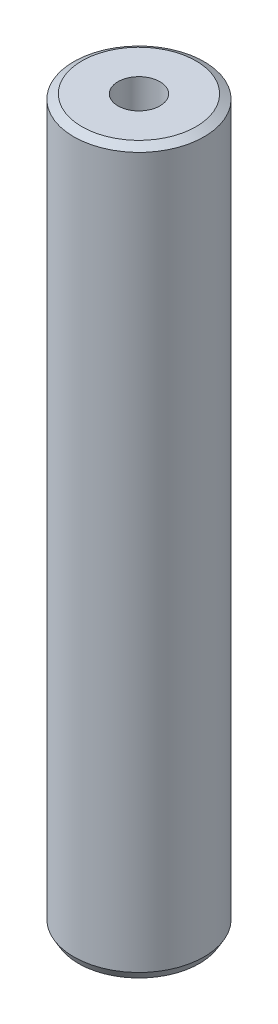
SolidWorks part; units mm, degrees
ref_plane "Front Plane" through (0, 0, 0) normal (0, 0, 1) x (1, 0, 0)
ref_plane "Top Plane" through (0, 0, 0) normal (0, 1, 0) x (1, 0, 0)
ref_plane "Right Plane" through (0, 0, 0) normal (1, 0, 0) x (0, 0, -1)
sketch "Sketch1" plane through (0, 0, 0) normal (0, 1, 0) x (1, 0, 0)
  circle A0 centre (0, 0) radius 25
  dimension "SHAFT_OD" = 50
extrude "Boss-Extrude1" add sketch "Sketch1" along normal blind 277.3595
sketch "Sketch2" plane through (0, 0, 0) normal (0, 1, 0) x (1, 0, 0)
  circle A0 centre (0, 0) radius 8.0588
  dimension "BORE_D" = 16.1175
extrude "Cut-Extrude1" cut sketch "Sketch2" along normal through all
chamfer "Chamfer1" distance 1.798 angle 60 2 edges at (0, 277.3595, 25) (0, 0, 25) first distance on face at (0, 277.3595, 25) first distance on face at (0, 0, 8.0588)
